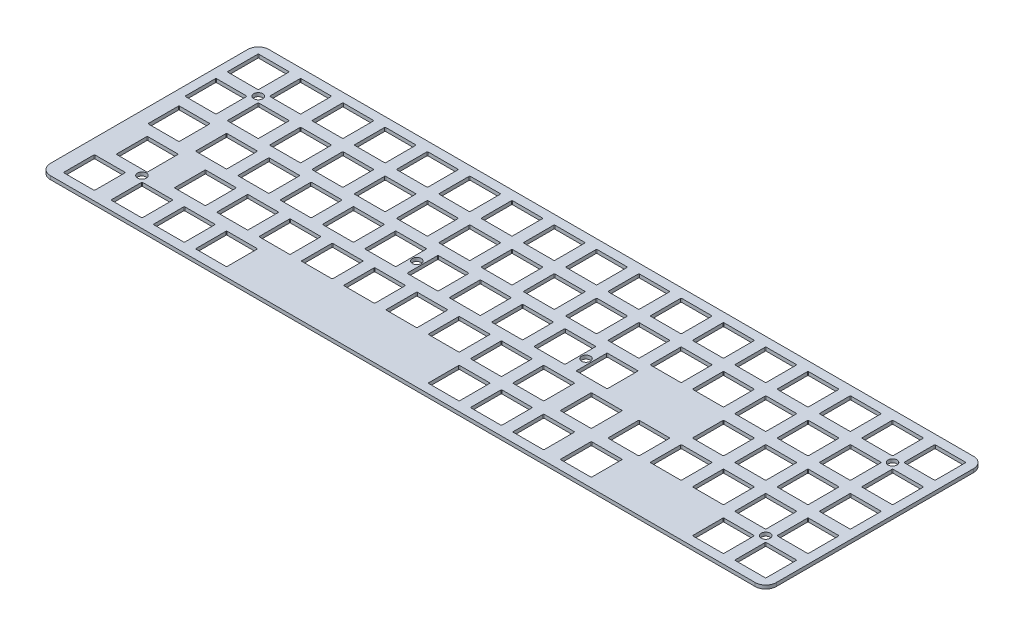
SolidWorks part; units mm, degrees
ref_plane "Front" through (0, 0, 0) normal (0, 0, 1) x (1, 0, 0)
ref_plane "Top" through (0, 0, 0) normal (0, 1, 0) x (1, 0, 0)
ref_plane "Right" through (0, 0, 0) normal (1, 0, 0) x (0, 0, -1)
sketch "Sketch1" plane through (0, 0, 0) normal (0, 1, 0) x (1, 0, 0)
  line L0 (-161.925, 28.575) -> (161.925, 28.575)
  line L1 (161.925, -47.625) -> (-161.925, -47.625)
  line L2 (161.925, -47.625) -> (161.925, 47.625)
  line L3 (161.925, 47.625) -> (-161.925, 47.625)
  line L4 (-161.925, -47.625) -> (-161.925, 47.625)
  line L5 (-123.825, 47.625) -> (-123.825, 28.575)
  line L6 (-104.775, 47.625) -> (-104.775, 28.575)
  line L7 (-142.875, 47.625) -> (-142.875, 28.575)
  line L8 (-85.725, 47.625) -> (-85.725, 28.575)
  line L9 (-66.675, 47.625) -> (-66.675, 28.575)
  line L10 (-47.625, 47.625) -> (-47.625, 28.575)
  line L11 (-28.575, 47.625) -> (-28.575, 28.575)
  line L12 (-9.525, 47.625) -> (-9.525, 28.575)
  line L13 (9.525, 47.625) -> (9.525, 28.575)
  line L14 (28.575, 47.625) -> (28.575, 28.575)
  line L15 (47.625, 47.625) -> (47.625, 28.575)
  line L16 (66.675, 47.625) -> (66.675, 28.575)
  line L17 (85.725, 47.625) -> (85.725, 28.575)
  line L18 (104.775, 47.625) -> (104.775, 28.575)
  line L19 (123.825, 47.625) -> (123.825, 28.575)
  line L20 (142.875, 47.625) -> (142.875, 28.575)
  line L21 (-142.875, 47.625) -> (-123.825, 47.625) construction
  line L22 (-161.925, 9.525) -> (161.925, 9.525)
  line L23 (-142.875, 28.575) -> (-142.875, 9.525)
  line L24 (-123.825, 28.575) -> (-123.825, 9.525)
  line L25 (-104.775, 28.575) -> (-104.775, 9.525)
  line L26 (-85.725, 28.575) -> (-85.725, 9.525)
  line L27 (-66.675, 28.575) -> (-66.675, 9.525)
  line L28 (-47.625, 28.575) -> (-47.625, 9.525)
  line L29 (-28.575, 28.575) -> (-28.575, 9.525)
  line L30 (-9.525, 28.575) -> (-9.525, 9.525)
  line L31 (9.525, 28.575) -> (9.525, 9.525)
  line L32 (28.575, 28.575) -> (28.575, 9.525)
  line L33 (47.625, 28.575) -> (47.625, 9.525)
  line L34 (66.675, 28.575) -> (66.675, 9.525)
  line L35 (85.725, 28.575) -> (85.725, 9.525)
  line L36 (104.775, 28.575) -> (104.775, 9.525)
  line L37 (123.825, 28.575) -> (123.825, 9.525)
  line L38 (142.875, 28.575) -> (142.875, 9.525)
  line L39 (-142.875, 28.575) -> (-123.825, 28.575) construction
  line L40 (-161.925, -9.525) -> (161.925, -9.525)
  line L41 (-161.925, -28.575) -> (161.925, -28.575)
  line L42 (-138.1125, 9.525) -> (-138.1125, -9.525)
  line L43 (-128.5875, -9.525) -> (-128.5875, -28.575)
  line L44 (-138.1125, -28.575) -> (-138.1125, -47.625)
  line L45 (-119.0625, 9.525) -> (-119.0625, -9.525)
  line L46 (-100.0125, 9.525) -> (-100.0125, -9.525)
  line L47 (-80.9625, 9.525) -> (-80.9625, -9.525)
  line L48 (-61.9125, 9.525) -> (-61.9125, -9.525)
  line L49 (-42.8625, 9.525) -> (-42.8625, -9.525)
  line L50 (-23.8125, 9.525) -> (-23.8125, -9.525)
  line L51 (-4.7625, 9.525) -> (-4.7625, -9.525)
  line L52 (14.2875, 9.525) -> (14.2875, -9.525)
  line L53 (33.3375, 9.525) -> (33.3375, -9.525)
  line L54 (-138.1125, 9.525) -> (-119.0625, 9.525) construction
  line L55 (52.3875, 9.525) -> (52.3875, -9.525)
  line L56 (85.725, 9.525) -> (85.725, -9.525)
  line L57 (-109.5375, -9.525) -> (-109.5375, -28.575)
  line L58 (-90.4875, -9.525) -> (-90.4875, -28.575)
  line L59 (-71.4375, -9.525) -> (-71.4375, -28.575)
  line L60 (-52.3875, -9.525) -> (-52.3875, -28.575)
  line L61 (-33.3375, -9.525) -> (-33.3375, -28.575)
  line L62 (-14.2875, -9.525) -> (-14.2875, -28.575)
  line L63 (4.7625, -9.525) -> (4.7625, -28.575)
  line L64 (23.8125, -9.525) -> (23.8125, -28.575)
  line L65 (42.8625, -9.525) -> (42.8625, -28.575)
  line L66 (-128.5875, -9.525) -> (-109.5375, -9.525) construction
  line L67 (66.675, -9.525) -> (66.675, -28.575)
  line L68 (85.725, -9.525) -> (85.725, -28.575)
  line L69 (-119.0625, -28.575) -> (-119.0625, -47.625)
  line L70 (-100.0125, -28.575) -> (-100.0125, -47.625)
  line L71 (-80.9625, -28.575) -> (-80.9625, -47.625)
  line L72 (-138.1125, -28.575) -> (-119.0625, -28.575) construction
  line L73 (-47.625, -28.575) -> (-47.625, -47.625)
  line L74 (4.7625, -28.575) -> (4.7625, -47.625)
  line L75 (23.8125, -28.575) -> (23.8125, -47.625)
  line L76 (42.8625, -28.575) -> (42.8625, -47.625)
  line L77 (61.9125, -28.575) -> (61.9125, -47.625)
  line L78 (85.725, -28.575) -> (85.725, -47.625)
  line L79 (104.775, 9.525) -> (104.775, -9.525)
  line L80 (104.775, -9.525) -> (104.775, -28.575)
  line L81 (123.825, 9.525) -> (123.825, -9.525)
  line L82 (123.825, -9.525) -> (123.825, -28.575)
  line L83 (123.825, -28.575) -> (123.825, -47.625)
  line L84 (142.875, 9.525) -> (142.875, -9.525)
  line L85 (142.875, -9.525) -> (142.875, -28.575)
  line L86 (142.875, -28.575) -> (142.875, -47.625)
  line L87 (-161.925, 47.625) -> (-142.875, 28.575) construction
  line L88 (-142.875, 28.575) -> (-161.925, 9.525) construction
  line L89 (-161.925, 9.525) -> (-138.1125, -9.525) construction
  line L90 (-138.1125, -9.525) -> (-119.0625, 9.525) construction
  line L91 (-119.0625, 9.525) -> (-100.0125, -9.525) construction
  line L92 (-100.0125, -9.525) -> (-80.9625, 9.525) construction
  line L93 (-80.9625, 9.525) -> (-61.9125, -9.525) construction
  line L94 (-61.9125, -9.525) -> (-42.8625, 9.525) construction
  line L95 (-42.8625, 9.525) -> (-23.8125, -9.525) construction
  line L96 (-23.8125, -9.525) -> (-4.7625, 9.525) construction
  line L97 (-4.7625, 9.525) -> (14.2875, -9.525) construction
  line L98 (14.2875, -9.525) -> (33.3375, 9.525) construction
  line L99 (33.3375, 9.525) -> (52.3875, -9.525) construction
  line L100 (52.3875, -9.525) -> (85.725, 9.525) construction
  line L101 (85.725, 9.525) -> (104.775, -9.525) construction
  line L102 (104.775, -9.525) -> (85.725, -28.575) construction
  line L103 (85.725, -47.625) -> (123.825, -28.575) construction
  line L104 (85.725, -28.575) -> (123.825, -47.625) construction
  line L105 (123.825, -28.575) -> (104.775, -9.525) construction
  line L106 (104.775, -9.525) -> (123.825, 9.525) construction
  line L107 (123.825, 9.525) -> (104.775, 28.575) construction
  line L108 (104.775, 28.575) -> (123.825, 47.625) construction
  line L109 (123.825, 47.625) -> (142.875, 28.575) construction
  line L110 (142.875, 28.575) -> (123.825, 9.525) construction
  line L111 (123.825, 9.525) -> (142.875, -9.525) construction
  line L112 (142.875, -9.525) -> (123.825, -28.575) construction
  line L113 (123.825, -28.575) -> (142.875, -47.625) construction
  line L114 (142.875, -47.625) -> (161.925, -28.575) construction
  line L115 (161.925, -28.575) -> (142.875, -9.525) construction
  line L116 (142.875, -9.525) -> (161.925, 9.525) construction
  line L117 (161.925, 9.525) -> (142.875, 28.575) construction
  line L118 (142.875, 28.575) -> (161.925, 47.625) construction
  line L119 (161.925, -47.625) -> (142.875, -28.575) construction
  line L120 (142.875, -28.575) -> (123.825, -47.625) construction
  line L121 (85.725, -47.625) -> (61.9125, -28.575) construction
  line L122 (61.9125, -28.575) -> (42.8625, -47.625) construction
  line L123 (42.8625, -47.625) -> (23.8125, -28.575) construction
  line L124 (23.8125, -28.575) -> (42.8625, -9.525) construction
  line L125 (42.8625, -9.525) -> (66.675, -28.575) construction
  line L126 (66.675, -28.575) -> (85.725, -9.525) construction
  line L127 (85.725, -9.525) -> (104.775, -28.575) construction
  line L128 (104.775, -28.575) -> (123.825, -9.525) construction
  line L129 (123.825, -9.525) -> (142.875, -28.575) construction
  line L130 (142.875, -28.575) -> (161.925, -9.525) construction
  line L131 (161.925, -9.525) -> (142.875, 9.525) construction
  line L132 (142.875, 9.525) -> (123.825, -9.525) construction
  line L133 (123.825, -9.525) -> (104.775, 9.525) construction
  line L134 (104.775, 9.525) -> (85.725, -9.525) construction
  line L135 (85.725, -9.525) -> (52.3875, 9.525) construction
  line L136 (52.3875, 9.525) -> (33.3375, -9.525) construction
  line L137 (33.3375, -9.525) -> (14.2875, 9.525) construction
  line L138 (14.2875, 9.525) -> (-4.7625, -9.525) construction
  line L139 (-4.7625, -9.525) -> (-23.8125, 9.525) construction
  line L140 (-23.8125, 9.525) -> (-42.8625, -9.525) construction
  line L141 (-42.8625, -9.525) -> (-61.9125, 9.525) construction
  line L142 (-61.9125, 9.525) -> (-80.9625, -9.525) construction
  line L143 (-80.9625, -9.525) -> (-100.0125, 9.525) construction
  line L144 (-100.0125, 9.525) -> (-119.0625, -9.525) construction
  line L145 (-119.0625, -9.525) -> (-138.1125, 9.525) construction
  line L146 (-138.1125, 9.525) -> (-161.925, -9.525) construction
  line L147 (-161.925, -9.525) -> (-128.5875, -28.575) construction
  line L148 (-128.5875, -28.575) -> (-109.5375, -9.525) construction
  line L149 (-109.5375, -9.525) -> (-90.4875, -28.575) construction
  line L150 (-90.4875, -28.575) -> (-71.4375, -9.525) construction
  line L151 (-71.4375, -9.525) -> (-52.3875, -28.575) construction
  line L152 (-52.3875, -28.575) -> (-33.3375, -9.525) construction
  line L153 (-33.3375, -9.525) -> (-14.2875, -28.575) construction
  line L154 (-14.2875, -28.575) -> (4.7625, -9.525) construction
  line L155 (4.7625, -9.525) -> (23.8125, -28.575) construction
  line L156 (23.8125, -28.575) -> (4.7625, -47.625) construction
  line L157 (4.7625, -47.625) -> (-47.625, -28.575) construction
  line L158 (-47.625, -28.575) -> (-80.9625, -47.625) construction
  line L159 (-80.9625, -47.625) -> (-100.0125, -28.575) construction
  line L160 (-100.0125, -28.575) -> (-119.0625, -47.625) construction
  line L161 (-119.0625, -47.625) -> (-138.1125, -28.575) construction
  line L162 (-138.1125, -28.575) -> (-161.925, -47.625) construction
  line L163 (-161.925, -28.575) -> (-138.1125, -47.625) construction
  line L164 (-138.1125, -47.625) -> (-119.0625, -28.575) construction
  line L165 (-119.0625, -28.575) -> (-100.0125, -47.625) construction
  line L166 (-100.0125, -47.625) -> (-80.9625, -28.575) construction
  line L167 (-80.9625, -28.575) -> (-47.625, -47.625) construction
  line L168 (-47.625, -47.625) -> (4.7625, -28.575) construction
  line L169 (4.7625, -28.575) -> (23.8125, -47.625) construction
  line L170 (23.8125, -47.625) -> (42.8625, -28.575) construction
  line L171 (42.8625, -28.575) -> (61.9125, -47.625) construction
  line L172 (61.9125, -47.625) -> (85.725, -28.575) construction
  line L173 (85.725, -28.575) -> (66.675, -9.525) construction
  line L174 (66.675, -9.525) -> (42.8625, -28.575) construction
  line L175 (42.8625, -28.575) -> (23.8125, -9.525) construction
  line L176 (23.8125, -9.525) -> (4.7625, -28.575) construction
  line L177 (4.7625, -28.575) -> (-14.2875, -9.525) construction
  line L178 (-14.2875, -9.525) -> (-33.3375, -28.575) construction
  line L179 (-33.3375, -28.575) -> (-52.3875, -9.525) construction
  line L180 (-52.3875, -9.525) -> (-71.4375, -28.575) construction
  line L181 (-71.4375, -28.575) -> (-90.4875, -9.525) construction
  line L182 (-90.4875, -9.525) -> (-109.5375, -28.575) construction
  line L183 (-109.5375, -28.575) -> (-128.5875, -9.525) construction
  line L184 (-128.5875, -9.525) -> (-161.925, -28.575) construction
  line L185 (161.925, 28.575) -> (142.875, 9.525) construction
  line L186 (142.875, 9.525) -> (123.825, 28.575) construction
  line L187 (123.825, 28.575) -> (104.775, 9.525) construction
  line L188 (104.775, 9.525) -> (85.725, 28.575) construction
  line L189 (85.725, 28.575) -> (66.675, 9.525) construction
  line L190 (66.675, 9.525) -> (47.625, 28.575) construction
  line L191 (47.625, 28.575) -> (28.575, 9.525) construction
  line L192 (28.575, 9.525) -> (9.525, 28.575) construction
  line L193 (9.525, 28.575) -> (-9.525, 9.525) construction
  line L194 (-9.525, 9.525) -> (-28.575, 28.575) construction
  line L195 (-28.575, 28.575) -> (-47.625, 9.525) construction
  line L196 (-47.625, 9.525) -> (-66.675, 28.575) construction
  line L197 (-66.675, 28.575) -> (-85.725, 9.525) construction
  line L198 (-85.725, 9.525) -> (-104.775, 28.575) construction
  line L199 (-104.775, 28.575) -> (-123.825, 9.525) construction
  line L200 (-123.825, 9.525) -> (-142.875, 28.575) construction
  line L201 (-161.925, 28.575) -> (-142.875, 9.525) construction
  line L202 (-142.875, 9.525) -> (-123.825, 28.575) construction
  line L203 (-123.825, 28.575) -> (-104.775, 9.525) construction
  line L204 (-104.775, 9.525) -> (-85.725, 28.575) construction
  line L205 (-85.725, 28.575) -> (-66.675, 9.525) construction
  line L206 (-66.675, 9.525) -> (-47.625, 28.575) construction
  line L207 (-47.625, 28.575) -> (-28.575, 9.525) construction
  line L208 (-28.575, 9.525) -> (-9.525, 28.575) construction
  line L209 (-9.525, 28.575) -> (9.525, 9.525) construction
  line L210 (9.525, 9.525) -> (28.575, 28.575) construction
  line L211 (28.575, 28.575) -> (47.625, 9.525) construction
  line L212 (47.625, 9.525) -> (66.675, 28.575) construction
  line L213 (66.675, 28.575) -> (85.725, 9.525) construction
  line L214 (85.725, 9.525) -> (104.775, 28.575) construction
  line L215 (161.925, 28.575) -> (142.875, 47.625) construction
  line L216 (142.875, 47.625) -> (123.825, 28.575) construction
  line L217 (123.825, 28.575) -> (104.775, 47.625) construction
  line L218 (104.775, 47.625) -> (85.725, 28.575) construction
  line L219 (85.725, 28.575) -> (66.675, 47.625) construction
  line L220 (66.675, 47.625) -> (47.625, 28.575) construction
  line L221 (47.625, 28.575) -> (28.575, 47.625) construction
  line L222 (28.575, 47.625) -> (9.525, 28.575) construction
  line L223 (9.525, 28.575) -> (-9.525, 47.625) construction
  line L224 (-9.525, 47.625) -> (-28.575, 28.575) construction
  line L225 (-28.575, 28.575) -> (-47.625, 47.625) construction
  line L226 (-47.625, 47.625) -> (-66.675, 28.575) construction
  line L227 (-66.675, 28.575) -> (-85.725, 47.625) construction
  line L228 (-85.725, 47.625) -> (-104.775, 28.575) construction
  line L229 (-104.775, 28.575) -> (-123.825, 47.625) construction
  line L230 (-123.825, 47.625) -> (-142.875, 28.575) construction
  line L231 (-161.925, 28.575) -> (-142.875, 47.625) construction
  line L232 (-142.875, 47.625) -> (-123.825, 28.575) construction
  line L233 (-123.825, 28.575) -> (-104.775, 47.625) construction
  line L234 (-104.775, 47.625) -> (-85.725, 28.575) construction
  line L235 (-85.725, 28.575) -> (-66.675, 47.625) construction
  line L236 (-66.675, 47.625) -> (-47.625, 28.575) construction
  line L237 (-47.625, 28.575) -> (-28.575, 47.625) construction
  line L238 (-28.575, 47.625) -> (-9.525, 28.575) construction
  line L239 (-9.525, 28.575) -> (9.525, 47.625) construction
  line L240 (9.525, 47.625) -> (28.575, 28.575) construction
  line L241 (28.575, 28.575) -> (47.625, 47.625) construction
  line L242 (47.625, 47.625) -> (66.675, 28.575) construction
  line L243 (66.675, 28.575) -> (85.725, 47.625) construction
  line L244 (85.725, 47.625) -> (104.775, 28.575) construction
  line L245 (160.147, 50.6095) -> (-160.147, 50.6095)
  line L246 (164.9095, 45.847) -> (164.9095, -45.847)
  line L247 (160.147, -50.6095) -> (-160.147, -50.6095)
  line L248 (-164.9095, 45.847) -> (-164.9095, -45.847)
  arc A0 (164.9095, 45.847) -> (160.147, 50.6095) centre (160.147, 45.847) ccw
  arc A1 (160.147, -50.6095) -> (164.9095, -45.847) centre (160.147, -45.847) ccw
  arc A2 (-164.9095, -45.847) -> (-160.147, -50.6095) centre (-160.147, -45.847) ccw
  arc A3 (-160.147, 50.6095) -> (-164.9095, 45.847) centre (-160.147, 45.847) ccw
  point P145 (0, 0)
  point P146 (104.775, -38.1)
  point P147 (-152.4, 38.1)
  point P148 (-152.4, 19.05)
  point P149 (-150.0188, 0)
  point P150 (-145.2562, -19.05)
  point P151 (-150.0188, -38.1)
  point P152 (-128.5875, -38.1)
  point P153 (-119.0625, -19.05)
  point P154 (-128.5875, 0)
  point P155 (-133.35, 19.05)
  point P156 (-133.35, 38.1)
  point P157 (-114.3, 38.1)
  point P158 (-114.3, 19.05)
  point P159 (-109.5375, 0)
  point P160 (-100.0125, -19.05)
  point P161 (-90.4875, -38.1)
  point P162 (-109.5375, -38.1)
  point P163 (-64.2938, -38.1)
  point P164 (-21.4312, -38.1)
  point P165 (14.2875, -38.1)
  point P166 (33.3375, -38.1)
  point P167 (52.3875, -38.1)
  point P168 (73.8188, -38.1)
  point P169 (133.35, -38.1)
  point P170 (152.4, -38.1)
  point P171 (152.4, -19.05)
  point P172 (133.35, -19.05)
  point P173 (114.3, -19.05)
  point P174 (95.25, -19.05)
  point P175 (76.2, -19.05)
  point P176 (54.7687, -19.05)
  point P177 (33.3375, -19.05)
  point P178 (14.2875, -19.05)
  point P179 (-4.7625, -19.05)
  point P180 (-23.8125, -19.05)
  point P181 (-42.8625, -19.05)
  point P182 (-61.9125, -19.05)
  point P183 (-80.9625, -19.05)
  point P184 (-90.4875, 0)
  point P185 (-71.4375, 0)
  point P186 (-52.3875, 0)
  point P187 (-33.3375, 0)
  point P188 (-14.2875, 0)
  point P189 (4.7625, 0)
  point P190 (23.8125, 0)
  point P191 (42.8625, 0)
  point P192 (69.0563, 0)
  point P193 (95.25, 0)
  point P194 (114.3, 0)
  point P195 (133.35, 0)
  point P196 (152.4, 0)
  point P197 (152.4, 19.05)
  point P198 (133.35, 19.05)
  point P199 (114.3, 19.05)
  point P200 (95.25, 19.05)
  point P201 (76.2, 19.05)
  point P202 (57.15, 19.05)
  point P203 (38.1, 19.05)
  point P204 (19.05, 19.05)
  point P205 (0, 19.05)
  point P206 (-19.05, 19.05)
  point P207 (-38.1, 19.05)
  point P208 (-57.15, 19.05)
  point P209 (-76.2, 19.05)
  point P210 (-95.25, 19.05)
  point P211 (-95.25, 38.1)
  point P212 (-76.2, 38.1)
  point P213 (-57.15, 38.1)
  point P214 (-38.1, 38.1)
  point P215 (-19.05, 38.1)
  point P216 (0, 38.1)
  point P217 (19.05, 38.1)
  point P218 (38.1, 38.1)
  point P219 (57.15, 38.1)
  point P220 (76.2, 38.1)
  point P221 (95.25, 38.1)
  point P222 (114.3, 38.1)
  point P223 (133.35, 38.1)
  point P224 (152.4, 38.1)
  point P225 (-152.4, 38.1)
  point P226 (0, 0)
sketch "Sketch2" plane through (0, 0, 0) normal (0, 1, 0) x (1, 0, 0)
  line L0 (-161.925, 28.575) -> (-142.875, 47.625) construction
  line L1 (-145.7071, 45.0977) -> (-159.0929, 45.0977)
  line L2 (-145.4023, 44.7929) -> (-145.4023, 31.4071)
  line L3 (-145.7071, 31.1023) -> (-159.0929, 31.1023)
  line L4 (-159.3977, 44.7929) -> (-159.3977, 31.4071)
  line L5 (-152.4, 31.1023) -> (-152.4, 45.0977) construction
  line L6 (-145.4023, 38.1) -> (-159.3977, 38.1) construction
  line L7 (-126.3523, 38.1) -> (-140.3477, 38.1) construction
  line L8 (-133.35, 31.1023) -> (-133.35, 45.0977) construction
  line L9 (-126.6571, 45.0977) -> (-140.0429, 45.0977)
  line L10 (-126.3523, 44.7929) -> (-126.3523, 31.4071)
  line L11 (-140.3477, 44.7929) -> (-140.3477, 31.4071)
  line L12 (-126.6571, 31.1023) -> (-140.0429, 31.1023)
  line L13 (-107.3023, 38.1) -> (-121.2977, 38.1) construction
  line L14 (-114.3, 31.1023) -> (-114.3, 45.0977) construction
  line L15 (-107.6071, 45.0977) -> (-120.9929, 45.0977)
  line L16 (-107.3023, 44.7929) -> (-107.3023, 31.4071)
  line L17 (-121.2977, 44.7929) -> (-121.2977, 31.4071)
  line L18 (-107.6071, 31.1023) -> (-120.9929, 31.1023)
  line L19 (-88.2523, 38.1) -> (-102.2477, 38.1) construction
  line L20 (-95.25, 31.1023) -> (-95.25, 45.0977) construction
  line L21 (-88.5571, 45.0977) -> (-101.9429, 45.0977)
  line L22 (-88.2523, 44.7929) -> (-88.2523, 31.4071)
  line L23 (-102.2477, 44.7929) -> (-102.2477, 31.4071)
  line L24 (-88.5571, 31.1023) -> (-101.9429, 31.1023)
  line L25 (-69.2023, 38.1) -> (-83.1977, 38.1) construction
  line L26 (-76.2, 31.1023) -> (-76.2, 45.0977) construction
  line L27 (-69.5071, 45.0977) -> (-82.8929, 45.0977)
  line L28 (-69.2023, 44.7929) -> (-69.2023, 31.4071)
  line L29 (-83.1977, 44.7929) -> (-83.1977, 31.4071)
  line L30 (-69.5071, 31.1023) -> (-82.8929, 31.1023)
  line L31 (-50.1523, 38.1) -> (-64.1477, 38.1) construction
  line L32 (-57.15, 31.1023) -> (-57.15, 45.0977) construction
  line L33 (-50.4571, 45.0977) -> (-63.8429, 45.0977)
  line L34 (-50.1523, 44.7929) -> (-50.1523, 31.4071)
  line L35 (-64.1477, 44.7929) -> (-64.1477, 31.4071)
  line L36 (-50.4571, 31.1023) -> (-63.8429, 31.1023)
  line L37 (-31.1023, 38.1) -> (-45.0977, 38.1) construction
  line L38 (-38.1, 31.1023) -> (-38.1, 45.0977) construction
  line L39 (-31.4071, 45.0977) -> (-44.7929, 45.0977)
  line L40 (-31.1023, 44.7929) -> (-31.1023, 31.4071)
  line L41 (-45.0977, 44.7929) -> (-45.0977, 31.4071)
  line L42 (-31.4071, 31.1023) -> (-44.7929, 31.1023)
  line L43 (-12.0523, 38.1) -> (-26.0477, 38.1) construction
  line L44 (-19.05, 31.1023) -> (-19.05, 45.0977) construction
  line L45 (-12.3571, 45.0977) -> (-25.7429, 45.0977)
  line L46 (-12.0523, 44.7929) -> (-12.0523, 31.4071)
  line L47 (-26.0477, 44.7929) -> (-26.0477, 31.4071)
  line L48 (-12.3571, 31.1023) -> (-25.7429, 31.1023)
  line L49 (6.9977, 38.1) -> (-6.9977, 38.1) construction
  line L50 (0, 31.1023) -> (0, 45.0977) construction
  line L51 (6.6929, 45.0977) -> (-6.6929, 45.0977)
  line L52 (6.9977, 44.7929) -> (6.9977, 31.4071)
  line L53 (-6.9977, 44.7929) -> (-6.9977, 31.4071)
  line L54 (6.6929, 31.1023) -> (-6.6929, 31.1023)
  line L55 (26.0477, 38.1) -> (12.0523, 38.1) construction
  line L56 (19.05, 31.1023) -> (19.05, 45.0977) construction
  line L57 (25.7429, 45.0977) -> (12.3571, 45.0977)
  line L58 (26.0477, 44.7929) -> (26.0477, 31.4071)
  line L59 (12.0523, 44.7929) -> (12.0523, 31.4071)
  line L60 (25.7429, 31.1023) -> (12.3571, 31.1023)
  line L61 (45.0977, 38.1) -> (31.1023, 38.1) construction
  line L62 (38.1, 31.1023) -> (38.1, 45.0977) construction
  line L63 (44.7929, 45.0977) -> (31.4071, 45.0977)
  line L64 (45.0977, 44.7929) -> (45.0977, 31.4071)
  line L65 (31.1023, 44.7929) -> (31.1023, 31.4071)
  line L66 (44.7929, 31.1023) -> (31.4071, 31.1023)
  line L67 (64.1477, 38.1) -> (50.1523, 38.1) construction
  line L68 (57.15, 31.1023) -> (57.15, 45.0977) construction
  line L69 (63.8429, 45.0977) -> (50.4571, 45.0977)
  line L70 (64.1477, 44.7929) -> (64.1477, 31.4071)
  line L71 (50.1523, 44.7929) -> (50.1523, 31.4071)
  line L72 (63.8429, 31.1023) -> (50.4571, 31.1023)
  line L73 (83.1977, 38.1) -> (69.2023, 38.1) construction
  line L74 (76.2, 31.1023) -> (76.2, 45.0977) construction
  line L75 (82.8929, 45.0977) -> (69.5071, 45.0977)
  line L76 (83.1977, 44.7929) -> (83.1977, 31.4071)
  line L77 (69.2023, 44.7929) -> (69.2023, 31.4071)
  line L78 (82.8929, 31.1023) -> (69.5071, 31.1023)
  line L79 (102.2477, 38.1) -> (88.2523, 38.1) construction
  line L80 (95.25, 31.1023) -> (95.25, 45.0977) construction
  line L81 (101.9429, 45.0977) -> (88.5571, 45.0977)
  line L82 (102.2477, 44.7929) -> (102.2477, 31.4071)
  line L83 (88.2523, 44.7929) -> (88.2523, 31.4071)
  line L84 (101.9429, 31.1023) -> (88.5571, 31.1023)
  line L85 (121.2977, 38.1) -> (107.3023, 38.1) construction
  line L86 (114.3, 31.1023) -> (114.3, 45.0977) construction
  line L87 (120.9929, 45.0977) -> (107.6071, 45.0977)
  line L88 (121.2977, 44.7929) -> (121.2977, 31.4071)
  line L89 (107.3023, 44.7929) -> (107.3023, 31.4071)
  line L90 (120.9929, 31.1023) -> (107.6071, 31.1023)
  line L91 (140.3477, 38.1) -> (126.3523, 38.1) construction
  line L92 (133.35, 31.1023) -> (133.35, 45.0977) construction
  line L93 (140.0429, 45.0977) -> (126.6571, 45.0977)
  line L94 (140.3477, 44.7929) -> (140.3477, 31.4071)
  line L95 (126.3523, 44.7929) -> (126.3523, 31.4071)
  line L96 (140.0429, 31.1023) -> (126.6571, 31.1023)
  line L97 (159.3977, 38.1) -> (145.4023, 38.1) construction
  line L98 (152.4, 31.1023) -> (152.4, 45.0977) construction
  line L99 (159.0929, 45.0977) -> (145.7071, 45.0977)
  line L100 (159.3977, 44.7929) -> (159.3977, 31.4071)
  line L101 (145.4023, 44.7929) -> (145.4023, 31.4071)
  line L102 (159.0929, 31.1023) -> (145.7071, 31.1023)
  line L103 (-126.3523, 19.05) -> (-140.3477, 19.05) construction
  line L104 (-133.35, 12.0523) -> (-133.35, 26.0477) construction
  line L105 (-126.6571, 26.0477) -> (-140.0429, 26.0477)
  line L106 (-126.3523, 25.7429) -> (-126.3523, 12.3571)
  line L107 (-140.3477, 25.7429) -> (-140.3477, 12.3571)
  line L108 (-126.6571, 12.0523) -> (-140.0429, 12.0523)
  line L109 (-107.3023, 19.05) -> (-121.2977, 19.05) construction
  line L110 (-114.3, 12.0523) -> (-114.3, 26.0477) construction
  line L111 (-107.6071, 26.0477) -> (-120.9929, 26.0477)
  line L112 (-107.3023, 25.7429) -> (-107.3023, 12.3571)
  line L113 (-121.2977, 25.7429) -> (-121.2977, 12.3571)
  line L114 (-107.6071, 12.0523) -> (-120.9929, 12.0523)
  line L115 (-88.2523, 19.05) -> (-102.2477, 19.05) construction
  line L116 (-95.25, 12.0523) -> (-95.25, 26.0477) construction
  line L117 (-88.5571, 26.0477) -> (-101.9429, 26.0477)
  line L118 (-88.2523, 25.7429) -> (-88.2523, 12.3571)
  line L119 (-102.2477, 25.7429) -> (-102.2477, 12.3571)
  line L120 (-88.5571, 12.0523) -> (-101.9429, 12.0523)
  line L121 (-69.2023, 19.05) -> (-83.1977, 19.05) construction
  line L122 (-76.2, 12.0523) -> (-76.2, 26.0477) construction
  line L123 (-69.5071, 26.0477) -> (-82.8929, 26.0477)
  line L124 (-69.2023, 25.7429) -> (-69.2023, 12.3571)
  line L125 (-83.1977, 25.7429) -> (-83.1977, 12.3571)
  line L126 (-69.5071, 12.0523) -> (-82.8929, 12.0523)
  line L127 (-50.1523, 19.05) -> (-64.1477, 19.05) construction
  line L128 (-57.15, 12.0523) -> (-57.15, 26.0477) construction
  line L129 (-50.4571, 26.0477) -> (-63.8429, 26.0477)
  line L130 (-50.1523, 25.7429) -> (-50.1523, 12.3571)
  line L131 (-64.1477, 25.7429) -> (-64.1477, 12.3571)
  line L132 (-50.4571, 12.0523) -> (-63.8429, 12.0523)
  line L133 (-31.1023, 19.05) -> (-45.0977, 19.05) construction
  line L134 (-38.1, 12.0523) -> (-38.1, 26.0477) construction
  line L135 (-31.4071, 26.0477) -> (-44.7929, 26.0477)
  line L136 (-31.1023, 25.7429) -> (-31.1023, 12.3571)
  line L137 (-45.0977, 25.7429) -> (-45.0977, 12.3571)
  line L138 (-31.4071, 12.0523) -> (-44.7929, 12.0523)
  line L139 (-12.0523, 19.05) -> (-26.0477, 19.05) construction
  line L140 (-19.05, 12.0523) -> (-19.05, 26.0477) construction
  line L141 (-12.3571, 26.0477) -> (-25.7429, 26.0477)
  line L142 (-12.0523, 25.7429) -> (-12.0523, 12.3571)
  line L143 (-26.0477, 25.7429) -> (-26.0477, 12.3571)
  line L144 (-12.3571, 12.0523) -> (-25.7429, 12.0523)
  line L145 (6.9977, 19.05) -> (-6.9977, 19.05) construction
  line L146 (0, 12.0523) -> (0, 26.0477) construction
  line L147 (6.6929, 26.0477) -> (-6.6929, 26.0477)
  line L148 (6.9977, 25.7429) -> (6.9977, 12.3571)
  line L149 (-6.9977, 25.7429) -> (-6.9977, 12.3571)
  line L150 (6.6929, 12.0523) -> (-6.6929, 12.0523)
  line L151 (26.0477, 19.05) -> (12.0523, 19.05) construction
  line L152 (19.05, 12.0523) -> (19.05, 26.0477) construction
  line L153 (25.7429, 26.0477) -> (12.3571, 26.0477)
  line L154 (26.0477, 25.7429) -> (26.0477, 12.3571)
  line L155 (12.0523, 25.7429) -> (12.0523, 12.3571)
  line L156 (25.7429, 12.0523) -> (12.3571, 12.0523)
  line L157 (45.0977, 19.05) -> (31.1023, 19.05) construction
  line L158 (38.1, 12.0523) -> (38.1, 26.0477) construction
  line L159 (44.7929, 26.0477) -> (31.4071, 26.0477)
  line L160 (45.0977, 25.7429) -> (45.0977, 12.3571)
  line L161 (31.1023, 25.7429) -> (31.1023, 12.3571)
  line L162 (44.7929, 12.0523) -> (31.4071, 12.0523)
  line L163 (64.1477, 19.05) -> (50.1523, 19.05) construction
  line L164 (57.15, 12.0523) -> (57.15, 26.0477) construction
  line L165 (63.8429, 26.0477) -> (50.4571, 26.0477)
  line L166 (64.1477, 25.7429) -> (64.1477, 12.3571)
  line L167 (50.1523, 25.7429) -> (50.1523, 12.3571)
  line L168 (63.8429, 12.0523) -> (50.4571, 12.0523)
  line L169 (83.1977, 19.05) -> (69.2023, 19.05) construction
  line L170 (76.2, 12.0523) -> (76.2, 26.0477) construction
  line L171 (82.8929, 26.0477) -> (69.5071, 26.0477)
  line L172 (83.1977, 25.7429) -> (83.1977, 12.3571)
  line L173 (69.2023, 25.7429) -> (69.2023, 12.3571)
  line L174 (82.8929, 12.0523) -> (69.5071, 12.0523)
  line L175 (102.2477, 19.05) -> (88.2523, 19.05) construction
  line L176 (95.25, 12.0523) -> (95.25, 26.0477) construction
  line L177 (101.9429, 26.0477) -> (88.5571, 26.0477)
  line L178 (102.2477, 25.7429) -> (102.2477, 12.3571)
  line L179 (88.2523, 25.7429) -> (88.2523, 12.3571)
  line L180 (101.9429, 12.0523) -> (88.5571, 12.0523)
  line L181 (121.2977, 19.05) -> (107.3023, 19.05) construction
  line L182 (114.3, 12.0523) -> (114.3, 26.0477) construction
  line L183 (120.9929, 26.0477) -> (107.6071, 26.0477)
  line L184 (121.2977, 25.7429) -> (121.2977, 12.3571)
  line L185 (107.3023, 25.7429) -> (107.3023, 12.3571)
  line L186 (120.9929, 12.0523) -> (107.6071, 12.0523)
  line L187 (140.3477, 19.05) -> (126.3523, 19.05) construction
  line L188 (133.35, 12.0523) -> (133.35, 26.0477) construction
  line L189 (140.0429, 26.0477) -> (126.6571, 26.0477)
  line L190 (140.3477, 25.7429) -> (140.3477, 12.3571)
  line L191 (126.3523, 25.7429) -> (126.3523, 12.3571)
  line L192 (140.0429, 12.0523) -> (126.6571, 12.0523)
  line L193 (159.3977, 19.05) -> (145.4023, 19.05) construction
  line L194 (152.4, 12.0523) -> (152.4, 26.0477) construction
  line L195 (159.0929, 26.0477) -> (145.7071, 26.0477)
  line L196 (159.3977, 25.7429) -> (159.3977, 12.3571)
  line L197 (145.4023, 25.7429) -> (145.4023, 12.3571)
  line L198 (159.0929, 12.0523) -> (145.7071, 12.0523)
  line L199 (-145.4023, 19.05) -> (-159.3977, 19.05) construction
  line L200 (-152.4, 12.0523) -> (-152.4, 26.0477) construction
  line L201 (-145.7071, 26.0477) -> (-159.0929, 26.0477)
  line L202 (-145.4023, 25.7429) -> (-145.4023, 12.3571)
  line L203 (-159.3977, 25.7429) -> (-159.3977, 12.3571)
  line L204 (-145.7071, 12.0523) -> (-159.0929, 12.0523)
  line L205 (-100.0125, -26.0477) -> (-100.0125, -12.0523) construction
  line L210 (-138.1125, 9.525) -> (-161.925, -9.525) construction
  line L211 (-157.0164, -6.9977) -> (-143.021, -6.9977)
  line L212 (-157.0164, -6.9977) -> (-157.0164, 6.9977)
  line L213 (-138.2585, -12.0523) -> (-152.254, -12.0523)
  line L214 (-138.2585, -12.0523) -> (-138.2585, -26.0477)
  line L215 (-138.2585, -26.0477) -> (-152.254, -26.0477)
  line L216 (-152.254, -12.0523) -> (-152.254, -26.0477)
  line L217 (-145.2562, -26.0477) -> (-145.2562, -12.0523) construction
  line L218 (-138.2586, -19.05) -> (-152.254, -19.05) construction
  line L219 (-157.0164, 6.9977) -> (-143.021, 6.9977)
  line L220 (-143.021, -6.9977) -> (-143.021, 6.9977)
  line L221 (-150.0187, 6.9977) -> (-150.0187, -6.9977) construction
  line L222 (-157.0164, 0) -> (-143.021, 0) construction
  line L223 (-138.1125, -28.575) -> (-161.925, -47.625) construction
  line L224 (-143.021, -31.1023) -> (-157.0164, -31.1023)
  line L225 (-143.021, -31.1023) -> (-143.021, -45.0977)
  line L226 (-143.021, -45.0977) -> (-157.0164, -45.0977)
  line L227 (-157.0164, -31.1023) -> (-157.0164, -45.0977)
  line L228 (-150.0187, -45.0977) -> (-150.0187, -31.1023) construction
  line L229 (-143.021, -38.1) -> (-157.0164, -38.1) construction
  line L230 (-128.5875, -28.575) -> (-109.5375, -9.525) construction
  line L231 (-121.5898, 6.9977) -> (-135.5852, 6.9977)
  line L232 (-121.5898, 6.9977) -> (-121.5898, -6.9977)
  line L233 (-121.5898, -6.9977) -> (-135.5852, -6.9977)
  line L234 (-135.5852, 6.9977) -> (-135.5852, -6.9977)
  line L235 (-128.5875, -6.9977) -> (-128.5875, 6.9977) construction
  line L236 (-121.5898, 0) -> (-135.5852, 0) construction
  line L237 (-112.0648, -12.0523) -> (-126.0602, -12.0523)
  line L238 (-112.0648, -12.0523) -> (-112.0648, -26.0477)
  line L239 (-112.0648, -26.0477) -> (-126.0602, -26.0477)
  line L240 (-126.0602, -12.0523) -> (-126.0602, -26.0477)
  line L241 (-119.0625, -26.0477) -> (-119.0625, -12.0523) construction
  line L242 (-112.0648, -19.05) -> (-126.0602, -19.05) construction
  line L243 (-138.1125, -47.625) -> (-119.0625, -28.575) construction
  line L244 (-135.5852, -45.0977) -> (-121.5898, -45.0977)
  line L245 (-135.5852, -45.0977) -> (-135.5852, -31.1023)
  line L246 (-135.5852, -31.1023) -> (-121.5898, -31.1023)
  line L247 (-121.5898, -45.0977) -> (-121.5898, -31.1023)
  line L248 (-128.5875, -31.1023) -> (-128.5875, -45.0977) construction
  line L249 (-135.5852, -38.1) -> (-121.5898, -38.1) construction
  line L250 (-102.5398, -6.9977) -> (-116.5352, -6.9977)
  line L251 (-102.5398, 6.9977) -> (-102.5398, -6.9977)
  line L252 (-102.5398, 6.9977) -> (-116.5352, 6.9977)
  line L253 (-116.5352, 6.9977) -> (-116.5352, -6.9977)
  line L254 (-102.5398, 0) -> (-116.5352, 0) construction
  line L255 (-109.5375, -6.9977) -> (-109.5375, 6.9977) construction
  line L256 (-83.4898, -6.9977) -> (-97.4852, -6.9977)
  line L257 (-83.4898, 6.9977) -> (-83.4898, -6.9977)
  line L258 (-83.4898, 6.9977) -> (-97.4852, 6.9977)
  line L259 (-97.4852, 6.9977) -> (-97.4852, -6.9977)
  line L260 (-83.4898, 0) -> (-97.4852, 0) construction
  line L261 (-90.4875, -6.9977) -> (-90.4875, 6.9977) construction
  line L262 (-64.4398, -6.9977) -> (-78.4352, -6.9977)
  line L263 (-64.4398, 6.9977) -> (-64.4398, -6.9977)
  line L264 (-64.4398, 6.9977) -> (-78.4352, 6.9977)
  line L265 (-78.4352, 6.9977) -> (-78.4352, -6.9977)
  line L266 (-64.4398, 0) -> (-78.4352, 0) construction
  line L267 (-71.4375, -6.9977) -> (-71.4375, 6.9977) construction
  line L268 (-45.3898, -6.9977) -> (-59.3852, -6.9977)
  line L269 (-45.3898, 6.9977) -> (-45.3898, -6.9977)
  line L270 (-45.3898, 6.9977) -> (-59.3852, 6.9977)
  line L271 (-59.3852, 6.9977) -> (-59.3852, -6.9977)
  line L272 (-45.3898, 0) -> (-59.3852, 0) construction
  line L273 (-52.3875, -6.9977) -> (-52.3875, 6.9977) construction
  line L274 (-26.3398, -6.9977) -> (-40.3352, -6.9977)
  line L275 (-26.3398, 6.9977) -> (-26.3398, -6.9977)
  line L276 (-26.3398, 6.9977) -> (-40.3352, 6.9977)
  line L277 (-40.3352, 6.9977) -> (-40.3352, -6.9977)
  line L278 (-26.3398, 0) -> (-40.3352, 0) construction
  line L279 (-33.3375, -6.9977) -> (-33.3375, 6.9977) construction
  line L280 (-7.2898, -6.9977) -> (-21.2852, -6.9977)
  line L281 (-7.2898, 6.9977) -> (-7.2898, -6.9977)
  line L282 (-7.2898, 6.9977) -> (-21.2852, 6.9977)
  line L283 (-21.2852, 6.9977) -> (-21.2852, -6.9977)
  line L284 (-7.2898, 0) -> (-21.2852, 0) construction
  line L285 (-14.2875, -6.9977) -> (-14.2875, 6.9977) construction
  line L286 (11.7602, -6.9977) -> (-2.2352, -6.9977)
  line L287 (11.7602, 6.9977) -> (11.7602, -6.9977)
  line L288 (11.7602, 6.9977) -> (-2.2352, 6.9977)
  line L289 (-2.2352, 6.9977) -> (-2.2352, -6.9977)
  line L290 (11.7602, 0) -> (-2.2352, 0) construction
  line L291 (4.7625, -6.9977) -> (4.7625, 6.9977) construction
  line L292 (30.8102, -6.9977) -> (16.8148, -6.9977)
  line L293 (30.8102, 6.9977) -> (30.8102, -6.9977)
  line L294 (30.8102, 6.9977) -> (16.8148, 6.9977)
  line L295 (16.8148, 6.9977) -> (16.8148, -6.9977)
  line L296 (30.8102, 0) -> (16.8148, 0) construction
  line L297 (23.8125, -6.9977) -> (23.8125, 6.9977) construction
  line L298 (49.8602, -6.9977) -> (35.8648, -6.9977)
  line L299 (49.8602, 6.9977) -> (49.8602, -6.9977)
  line L300 (49.8602, 6.9977) -> (35.8648, 6.9977)
  line L301 (35.8648, 6.9977) -> (35.8648, -6.9977)
  line L302 (49.8602, 0) -> (35.8648, 0) construction
  line L303 (42.8625, -6.9977) -> (42.8625, 6.9977) construction
  line L304 (-93.0148, -19.05) -> (-107.0102, -19.05) construction
  line L305 (-93.0148, -12.0523) -> (-107.0102, -12.0523)
  line L306 (-93.0148, -12.0523) -> (-93.0148, -26.0477)
  line L307 (-93.0148, -26.0477) -> (-107.0102, -26.0477)
  line L308 (-107.0102, -12.0523) -> (-107.0102, -26.0477)
  line L309 (-80.9625, -26.0477) -> (-80.9625, -12.0523) construction
  line L310 (-73.9648, -19.05) -> (-87.9602, -19.05) construction
  line L311 (-73.9648, -12.0523) -> (-87.9602, -12.0523)
  line L312 (-73.9648, -12.0523) -> (-73.9648, -26.0477)
  line L313 (-73.9648, -26.0477) -> (-87.9602, -26.0477)
  line L314 (-87.9602, -12.0523) -> (-87.9602, -26.0477)
  line L315 (-61.9125, -26.0477) -> (-61.9125, -12.0523) construction
  line L316 (-54.9148, -19.05) -> (-68.9102, -19.05) construction
  line L317 (-54.9148, -12.0523) -> (-68.9102, -12.0523)
  line L318 (-54.9148, -12.0523) -> (-54.9148, -26.0477)
  line L319 (-54.9148, -26.0477) -> (-68.9102, -26.0477)
  line L320 (-68.9102, -12.0523) -> (-68.9102, -26.0477)
  line L321 (-42.8625, -26.0477) -> (-42.8625, -12.0523) construction
  line L322 (-35.8648, -19.05) -> (-49.8602, -19.05) construction
  line L323 (-35.8648, -12.0523) -> (-49.8602, -12.0523)
  line L324 (-35.8648, -12.0523) -> (-35.8648, -26.0477)
  line L325 (-35.8648, -26.0477) -> (-49.8602, -26.0477)
  line L326 (-49.8602, -12.0523) -> (-49.8602, -26.0477)
  line L327 (-23.8125, -26.0477) -> (-23.8125, -12.0523) construction
  line L328 (-16.8148, -19.05) -> (-30.8102, -19.05) construction
  line L329 (-16.8148, -12.0523) -> (-30.8102, -12.0523)
  line L330 (-16.8148, -12.0523) -> (-16.8148, -26.0477)
  line L331 (-16.8148, -26.0477) -> (-30.8102, -26.0477)
  line L332 (-30.8102, -12.0523) -> (-30.8102, -26.0477)
  line L333 (-4.7625, -26.0477) -> (-4.7625, -12.0523) construction
  line L334 (2.2352, -19.05) -> (-11.7602, -19.05) construction
  line L335 (2.2352, -12.0523) -> (-11.7602, -12.0523)
  line L336 (2.2352, -12.0523) -> (2.2352, -26.0477)
  line L337 (2.2352, -26.0477) -> (-11.7602, -26.0477)
  line L338 (-11.7602, -12.0523) -> (-11.7602, -26.0477)
  line L339 (14.2875, -26.0477) -> (14.2875, -12.0523) construction
  line L340 (21.2852, -19.05) -> (7.2898, -19.05) construction
  line L341 (21.2852, -12.0523) -> (7.2898, -12.0523)
  line L342 (21.2852, -12.0523) -> (21.2852, -26.0477)
  line L343 (21.2852, -26.0477) -> (7.2898, -26.0477)
  line L344 (7.2898, -12.0523) -> (7.2898, -26.0477)
  line L345 (33.3375, -26.0477) -> (33.3375, -12.0523) construction
  line L346 (40.3352, -19.05) -> (26.3398, -19.05) construction
  line L347 (40.3352, -12.0523) -> (26.3398, -12.0523)
  line L348 (40.3352, -12.0523) -> (40.3352, -26.0477)
  line L349 (40.3352, -26.0477) -> (26.3398, -26.0477)
  line L350 (26.3398, -12.0523) -> (26.3398, -26.0477)
  line L353 (-100.0125, -28.575) -> (-119.0625, -47.625) construction
  line L354 (-116.5352, -45.0977) -> (-102.5398, -45.0977)
  line L358 (-116.5352, -45.0977) -> (-116.5352, -31.1023)
  line L359 (-116.5352, -31.1023) -> (-102.5398, -31.1023)
  line L362 (-102.5398, -45.0977) -> (-102.5398, -31.1023)
  line L364 (-109.5375, -31.1023) -> (-109.5375, -45.0977) construction
  line L371 (-116.5352, -38.1) -> (-102.5398, -38.1) construction
  line L373 (-100.0125, -47.625) -> (-80.9625, -28.575) construction
  line L376 (-97.4852, -45.0977) -> (-83.4898, -45.0977)
  line L378 (-97.4852, -45.0977) -> (-97.4852, -31.1023)
  line L381 (101.9429, -6.9977) -> (88.5571, -6.9977)
  line L382 (-97.4852, -31.1023) -> (-83.4898, -31.1023)
  line L383 (-83.4898, -45.0977) -> (-83.4898, -31.1023)
  line L384 (-90.4875, -31.1023) -> (-90.4875, -45.0977) construction
  line L385 (-97.4852, -38.1) -> (-83.4898, -38.1) construction
  line L386 (23.8125, -47.625) -> (42.8625, -28.575) construction
  line L387 (7.2898, -45.0977) -> (21.2852, -45.0977)
  line L388 (7.2898, -45.0977) -> (7.2898, -31.1023)
  line L389 (7.2898, -31.1023) -> (21.2852, -31.1023)
  line L390 (21.2852, -45.0977) -> (21.2852, -31.1023)
  line L391 (14.2875, -31.1023) -> (14.2875, -45.0977) construction
  line L392 (7.2898, -38.1) -> (21.2852, -38.1) construction
  line L393 (26.3398, -45.0977) -> (40.3352, -45.0977)
  line L394 (26.3398, -45.0977) -> (26.3398, -31.1023)
  line L395 (26.3398, -31.1023) -> (40.3352, -31.1023)
  line L396 (40.3352, -45.0977) -> (40.3352, -31.1023)
  line L397 (33.3375, -31.1023) -> (33.3375, -45.0977) construction
  line L398 (26.3398, -38.1) -> (40.3352, -38.1) construction
  line L399 (61.9125, -28.575) -> (42.8625, -47.625) construction
  line L400 (45.3898, -45.0977) -> (59.3852, -45.0977)
  line L401 (45.3898, -45.0977) -> (45.3898, -31.1023)
  line L402 (45.3898, -31.1023) -> (59.3852, -31.1023)
  line L403 (59.3852, -45.0977) -> (59.3852, -31.1023)
  line L404 (52.3875, -31.1023) -> (52.3875, -45.0977) construction
  line L405 (45.3898, -38.1) -> (59.3852, -38.1) construction
  line L406 (102.2477, 6.6929) -> (102.2477, -6.6929)
  line L407 (66.821, -45.0977) -> (80.8165, -45.0977)
  line L408 (66.821, -45.0977) -> (66.821, -31.1023)
  line L409 (66.821, -31.1023) -> (80.8165, -31.1023)
  line L410 (80.8165, -45.0977) -> (80.8165, -31.1023)
  line L411 (73.8188, -31.1023) -> (73.8188, -45.0977) construction
  line L412 (66.821, -38.1) -> (80.8165, -38.1) construction
  line L413 (101.9429, 6.9977) -> (88.5571, 6.9977)
  line L414 (88.2523, 6.6929) -> (88.2523, -6.6929)
  line L415 (95.25, -6.9977) -> (95.25, 6.9977) construction
  line L416 (102.2477, 0) -> (88.2523, 0) construction
  line L417 (120.9929, -6.9977) -> (107.6071, -6.9977)
  line L418 (114.3, -6.9977) -> (114.3, 6.9977) construction
  line L419 (121.2977, 0) -> (107.3023, 0) construction
  line L420 (120.9929, 6.9977) -> (107.6071, 6.9977)
  line L421 (107.3023, 6.6929) -> (107.3023, -6.6929)
  line L422 (121.2977, 6.6929) -> (121.2977, -6.6929)
  line L423 (140.0429, 6.9977) -> (126.6571, 6.9977)
  line L424 (126.3523, 6.6929) -> (126.3523, -6.6929)
  line L425 (133.35, -6.9977) -> (133.35, 6.9977) construction
  line L426 (140.3477, 0) -> (126.3523, 0) construction
  line L427 (140.3477, 6.6929) -> (140.3477, -6.6929)
  line L428 (140.0429, -6.9977) -> (126.6571, -6.9977)
  line L429 (159.3977, 6.6929) -> (159.3977, -6.6929)
  line L430 (159.0929, -6.9977) -> (145.7071, -6.9977)
  line L431 (152.4, -6.9977) -> (152.4, 6.9977) construction
  line L432 (145.4023, 6.6929) -> (145.4023, -6.6929)
  line L433 (159.3977, 0) -> (145.4023, 0) construction
  line L434 (159.0929, 6.9977) -> (145.7071, 6.9977)
  line L435 (101.9429, -26.0477) -> (88.5571, -26.0477)
  line L436 (102.2477, -12.3571) -> (102.2477, -25.7429)
  line L437 (101.9429, -12.0523) -> (88.5571, -12.0523)
  line L438 (88.2523, -12.3571) -> (88.2523, -25.7429)
  line L439 (95.25, -26.0477) -> (95.25, -12.0523) construction
  line L440 (102.2477, -19.05) -> (88.2523, -19.05) construction
  line L441 (120.9929, -26.0477) -> (107.6071, -26.0477)
  line L442 (114.3, -26.0477) -> (114.3, -12.0523) construction
  line L443 (121.2977, -19.05) -> (107.3023, -19.05) construction
  line L444 (120.9929, -12.0523) -> (107.6071, -12.0523)
  line L445 (107.3023, -12.3571) -> (107.3023, -25.7429)
  line L446 (121.2977, -12.3571) -> (121.2977, -25.7429)
  line L447 (140.0429, -12.0523) -> (126.6571, -12.0523)
  line L448 (126.3523, -12.3571) -> (126.3523, -25.7429)
  line L449 (133.35, -26.0477) -> (133.35, -12.0523) construction
  line L450 (140.3477, -19.05) -> (126.3523, -19.05) construction
  line L451 (140.3477, -12.3571) -> (140.3477, -25.7429)
  line L452 (140.0429, -26.0477) -> (126.6571, -26.0477)
  line L453 (159.3977, -12.3571) -> (159.3977, -25.7429)
  line L454 (159.0929, -26.0477) -> (145.7071, -26.0477)
  line L455 (152.4, -26.0477) -> (152.4, -12.0523) construction
  line L456 (145.4023, -12.3571) -> (145.4023, -25.7429)
  line L457 (159.3977, -19.05) -> (145.4023, -19.05) construction
  line L458 (159.0929, -12.0523) -> (145.7071, -12.0523)
  line L459 (85.725, -28.575) -> (66.675, -9.525) construction
  line L460 (145.4023, -45.0977) -> (159.3977, -45.0977)
  line L461 (145.4023, -45.0977) -> (145.4023, -31.1023)
  line L462 (145.4023, -31.1023) -> (159.3977, -31.1023)
  line L463 (159.3977, -45.0977) -> (159.3977, -31.1023)
  line L464 (152.4, -31.1023) -> (152.4, -45.0977) construction
  line L465 (145.4023, -38.1) -> (159.3977, -38.1) construction
  line L466 (126.3523, -45.0977) -> (140.3477, -45.0977)
  line L467 (126.3523, -45.0977) -> (126.3523, -31.1023)
  line L468 (126.3523, -31.1023) -> (140.3477, -31.1023)
  line L469 (140.3477, -45.0977) -> (140.3477, -31.1023)
  line L470 (133.35, -31.1023) -> (133.35, -45.0977) construction
  line L471 (126.3523, -38.1) -> (140.3477, -38.1) construction
  line L472 (69.2023, -26.0477) -> (83.1977, -26.0477)
  line L473 (69.2023, -26.0477) -> (69.2023, -12.0523)
  line L474 (69.2023, -12.0523) -> (83.1977, -12.0523)
  line L475 (83.1977, -26.0477) -> (83.1977, -12.0523)
  line L476 (76.2, -12.0523) -> (76.2, -26.0477) construction
  line L477 (69.2023, -19.05) -> (83.1977, -19.05) construction
  line L478 (-145.7071, 31.4071) -> (-140.0429, 25.7429) construction
  line L479 (47.771, -26.0477) -> (61.7665, -26.0477)
  line L480 (47.771, -26.0477) -> (47.771, -12.0523)
  line L481 (47.771, -12.0523) -> (61.7665, -12.0523)
  line L482 (61.7665, -26.0477) -> (61.7665, -12.0523)
  line L483 (54.7687, -12.0523) -> (54.7687, -26.0477) construction
  line L484 (47.771, -19.05) -> (61.7665, -19.05) construction
  line L489 (-140.0429, 31.4071) -> (-145.7071, 25.7429) construction
  line L490 (158.75, -49.2125) -> (-158.75, -49.2125)
  line L491 (140.0429, 31.4071) -> (145.7071, 25.7429) construction
  line L496 (163.5125, -44.45) -> (163.5125, 44.45)
  line L497 (158.75, 49.2125) -> (-158.75, 49.2125)
  line L498 (145.7071, 31.4071) -> (140.0429, 25.7429) construction
  line L503 (-163.5125, -44.45) -> (-163.5125, 44.45)
  line L504 (0, 49.2125) -> (0, -49.2125) construction
  line L505 (-45.3898, 6.9977) -> (-40.3352, 6.9977) construction
  line L510 (163.5125, 0) -> (-163.5125, 0) construction
  line L511 (-42.8625, 6.9977) -> (-42.8625, 0) construction
  line L512 (30.8102, 6.9977) -> (35.8648, 6.9977) construction
  line L513 (33.3375, 6.9977) -> (33.3375, 0) construction
  arc A0 (-145.4023, 31.4071) -> (-145.7071, 31.1023) centre (-145.7071, 31.4071) cw
  arc A1 (-145.7071, 45.0977) -> (-145.4023, 44.7929) centre (-145.7071, 44.7929) cw
  arc A2 (-159.0929, 45.0977) -> (-159.3977, 44.7929) centre (-159.0929, 44.7929) ccw
  arc A3 (-159.0929, 31.1023) -> (-159.3977, 31.4071) centre (-159.0929, 31.4071) cw
  arc A4 (-126.6571, 45.0977) -> (-126.3523, 44.7929) centre (-126.6571, 44.7929) cw
  arc A5 (-140.0429, 45.0977) -> (-140.3477, 44.7929) centre (-140.0429, 44.7929) ccw
  arc A6 (-140.0429, 31.1023) -> (-140.3477, 31.4071) centre (-140.0429, 31.4071) cw
  arc A7 (-126.3523, 31.4071) -> (-126.6571, 31.1023) centre (-126.6571, 31.4071) cw
  arc A8 (-107.6071, 45.0977) -> (-107.3023, 44.7929) centre (-107.6071, 44.7929) cw
  arc A9 (-120.9929, 45.0977) -> (-121.2977, 44.7929) centre (-120.9929, 44.7929) ccw
  arc A10 (-120.9929, 31.1023) -> (-121.2977, 31.4071) centre (-120.9929, 31.4071) cw
  arc A11 (-107.3023, 31.4071) -> (-107.6071, 31.1023) centre (-107.6071, 31.4071) cw
  arc A12 (-88.5571, 45.0977) -> (-88.2523, 44.7929) centre (-88.5571, 44.7929) cw
  arc A13 (-101.9429, 45.0977) -> (-102.2477, 44.7929) centre (-101.9429, 44.7929) ccw
  arc A14 (-101.9429, 31.1023) -> (-102.2477, 31.4071) centre (-101.9429, 31.4071) cw
  arc A15 (-88.2523, 31.4071) -> (-88.5571, 31.1023) centre (-88.5571, 31.4071) cw
  arc A16 (-69.5071, 45.0977) -> (-69.2023, 44.7929) centre (-69.5071, 44.7929) cw
  arc A17 (-82.8929, 45.0977) -> (-83.1977, 44.7929) centre (-82.8929, 44.7929) ccw
  arc A18 (-82.8929, 31.1023) -> (-83.1977, 31.4071) centre (-82.8929, 31.4071) cw
  arc A19 (-69.2023, 31.4071) -> (-69.5071, 31.1023) centre (-69.5071, 31.4071) cw
  arc A20 (-50.4571, 45.0977) -> (-50.1523, 44.7929) centre (-50.4571, 44.7929) cw
  arc A21 (-63.8429, 45.0977) -> (-64.1477, 44.7929) centre (-63.8429, 44.7929) ccw
  arc A22 (-63.8429, 31.1023) -> (-64.1477, 31.4071) centre (-63.8429, 31.4071) cw
  arc A23 (-50.1523, 31.4071) -> (-50.4571, 31.1023) centre (-50.4571, 31.4071) cw
  arc A24 (-31.4071, 45.0977) -> (-31.1023, 44.7929) centre (-31.4071, 44.7929) cw
  arc A25 (-44.7929, 45.0977) -> (-45.0977, 44.7929) centre (-44.7929, 44.7929) ccw
  arc A26 (-44.7929, 31.1023) -> (-45.0977, 31.4071) centre (-44.7929, 31.4071) cw
  arc A27 (-31.1023, 31.4071) -> (-31.4071, 31.1023) centre (-31.4071, 31.4071) cw
  arc A28 (-12.3571, 45.0977) -> (-12.0523, 44.7929) centre (-12.3571, 44.7929) cw
  arc A29 (-25.7429, 45.0977) -> (-26.0477, 44.7929) centre (-25.7429, 44.7929) ccw
  arc A30 (-25.7429, 31.1023) -> (-26.0477, 31.4071) centre (-25.7429, 31.4071) cw
  arc A31 (-12.0523, 31.4071) -> (-12.3571, 31.1023) centre (-12.3571, 31.4071) cw
  arc A32 (6.6929, 45.0977) -> (6.9977, 44.7929) centre (6.6929, 44.7929) cw
  arc A33 (-6.6929, 45.0977) -> (-6.9977, 44.7929) centre (-6.6929, 44.7929) ccw
  arc A34 (-6.6929, 31.1023) -> (-6.9977, 31.4071) centre (-6.6929, 31.4071) cw
  arc A35 (6.9977, 31.4071) -> (6.6929, 31.1023) centre (6.6929, 31.4071) cw
  arc A36 (25.7429, 45.0977) -> (26.0477, 44.7929) centre (25.7429, 44.7929) cw
  arc A37 (12.3571, 45.0977) -> (12.0523, 44.7929) centre (12.3571, 44.7929) ccw
  arc A38 (12.3571, 31.1023) -> (12.0523, 31.4071) centre (12.3571, 31.4071) cw
  arc A39 (26.0477, 31.4071) -> (25.7429, 31.1023) centre (25.7429, 31.4071) cw
  arc A40 (44.7929, 45.0977) -> (45.0977, 44.7929) centre (44.7929, 44.7929) cw
  arc A41 (31.4071, 45.0977) -> (31.1023, 44.7929) centre (31.4071, 44.7929) ccw
  arc A42 (31.4071, 31.1023) -> (31.1023, 31.4071) centre (31.4071, 31.4071) cw
  arc A43 (45.0977, 31.4071) -> (44.7929, 31.1023) centre (44.7929, 31.4071) cw
  arc A44 (63.8429, 45.0977) -> (64.1477, 44.7929) centre (63.8429, 44.7929) cw
  arc A45 (50.4571, 45.0977) -> (50.1523, 44.7929) centre (50.4571, 44.7929) ccw
  arc A46 (50.4571, 31.1023) -> (50.1523, 31.4071) centre (50.4571, 31.4071) cw
  arc A47 (64.1477, 31.4071) -> (63.8429, 31.1023) centre (63.8429, 31.4071) cw
  arc A48 (82.8929, 45.0977) -> (83.1977, 44.7929) centre (82.8929, 44.7929) cw
  arc A49 (69.5071, 45.0977) -> (69.2023, 44.7929) centre (69.5071, 44.7929) ccw
  arc A50 (69.5071, 31.1023) -> (69.2023, 31.4071) centre (69.5071, 31.4071) cw
  arc A51 (83.1977, 31.4071) -> (82.8929, 31.1023) centre (82.8929, 31.4071) cw
  arc A52 (101.9429, 45.0977) -> (102.2477, 44.7929) centre (101.9429, 44.7929) cw
  arc A53 (88.5571, 45.0977) -> (88.2523, 44.7929) centre (88.5571, 44.7929) ccw
  arc A54 (88.5571, 31.1023) -> (88.2523, 31.4071) centre (88.5571, 31.4071) cw
  arc A55 (102.2477, 31.4071) -> (101.9429, 31.1023) centre (101.9429, 31.4071) cw
  arc A56 (120.9929, 45.0977) -> (121.2977, 44.7929) centre (120.9929, 44.7929) cw
  arc A57 (107.6071, 45.0977) -> (107.3023, 44.7929) centre (107.6071, 44.7929) ccw
  arc A58 (107.6071, 31.1023) -> (107.3023, 31.4071) centre (107.6071, 31.4071) cw
  arc A59 (121.2977, 31.4071) -> (120.9929, 31.1023) centre (120.9929, 31.4071) cw
  arc A60 (140.0429, 45.0977) -> (140.3477, 44.7929) centre (140.0429, 44.7929) cw
  arc A61 (126.6571, 45.0977) -> (126.3523, 44.7929) centre (126.6571, 44.7929) ccw
  arc A62 (126.6571, 31.1023) -> (126.3523, 31.4071) centre (126.6571, 31.4071) cw
  arc A63 (140.3477, 31.4071) -> (140.0429, 31.1023) centre (140.0429, 31.4071) cw
  arc A64 (159.0929, 45.0977) -> (159.3977, 44.7929) centre (159.0929, 44.7929) cw
  arc A65 (145.7071, 45.0977) -> (145.4023, 44.7929) centre (145.7071, 44.7929) ccw
  arc A66 (145.7071, 31.1023) -> (145.4023, 31.4071) centre (145.7071, 31.4071) cw
  arc A67 (159.3977, 31.4071) -> (159.0929, 31.1023) centre (159.0929, 31.4071) cw
  arc A68 (-126.6571, 26.0477) -> (-126.3523, 25.7429) centre (-126.6571, 25.7429) cw
  arc A69 (-140.0429, 26.0477) -> (-140.3477, 25.7429) centre (-140.0429, 25.7429) ccw
  arc A70 (-140.0429, 12.0523) -> (-140.3477, 12.3571) centre (-140.0429, 12.3571) cw
  arc A71 (-126.3523, 12.3571) -> (-126.6571, 12.0523) centre (-126.6571, 12.3571) cw
  arc A72 (-107.6071, 26.0477) -> (-107.3023, 25.7429) centre (-107.6071, 25.7429) cw
  arc A73 (-120.9929, 26.0477) -> (-121.2977, 25.7429) centre (-120.9929, 25.7429) ccw
  arc A74 (-120.9929, 12.0523) -> (-121.2977, 12.3571) centre (-120.9929, 12.3571) cw
  arc A75 (-107.3023, 12.3571) -> (-107.6071, 12.0523) centre (-107.6071, 12.3571) cw
  arc A76 (-88.5571, 26.0477) -> (-88.2523, 25.7429) centre (-88.5571, 25.7429) cw
  arc A77 (-101.9429, 26.0477) -> (-102.2477, 25.7429) centre (-101.9429, 25.7429) ccw
  arc A78 (-101.9429, 12.0523) -> (-102.2477, 12.3571) centre (-101.9429, 12.3571) cw
  arc A79 (-88.2523, 12.3571) -> (-88.5571, 12.0523) centre (-88.5571, 12.3571) cw
  arc A80 (-69.5071, 26.0477) -> (-69.2023, 25.7429) centre (-69.5071, 25.7429) cw
  arc A81 (-82.8929, 26.0477) -> (-83.1977, 25.7429) centre (-82.8929, 25.7429) ccw
  arc A82 (-82.8929, 12.0523) -> (-83.1977, 12.3571) centre (-82.8929, 12.3571) cw
  arc A83 (-69.2023, 12.3571) -> (-69.5071, 12.0523) centre (-69.5071, 12.3571) cw
  arc A84 (-50.4571, 26.0477) -> (-50.1523, 25.7429) centre (-50.4571, 25.7429) cw
  arc A85 (-63.8429, 26.0477) -> (-64.1477, 25.7429) centre (-63.8429, 25.7429) ccw
  arc A86 (-63.8429, 12.0523) -> (-64.1477, 12.3571) centre (-63.8429, 12.3571) cw
  arc A87 (-50.1523, 12.3571) -> (-50.4571, 12.0523) centre (-50.4571, 12.3571) cw
  arc A88 (-31.4071, 26.0477) -> (-31.1023, 25.7429) centre (-31.4071, 25.7429) cw
  arc A89 (-44.7929, 26.0477) -> (-45.0977, 25.7429) centre (-44.7929, 25.7429) ccw
  arc A90 (-44.7929, 12.0523) -> (-45.0977, 12.3571) centre (-44.7929, 12.3571) cw
  arc A91 (-31.1023, 12.3571) -> (-31.4071, 12.0523) centre (-31.4071, 12.3571) cw
  arc A92 (-12.3571, 26.0477) -> (-12.0523, 25.7429) centre (-12.3571, 25.7429) cw
  arc A93 (-25.7429, 26.0477) -> (-26.0477, 25.7429) centre (-25.7429, 25.7429) ccw
  arc A94 (-25.7429, 12.0523) -> (-26.0477, 12.3571) centre (-25.7429, 12.3571) cw
  arc A95 (-12.0523, 12.3571) -> (-12.3571, 12.0523) centre (-12.3571, 12.3571) cw
  arc A96 (6.6929, 26.0477) -> (6.9977, 25.7429) centre (6.6929, 25.7429) cw
  arc A97 (-6.6929, 26.0477) -> (-6.9977, 25.7429) centre (-6.6929, 25.7429) ccw
  arc A98 (-6.6929, 12.0523) -> (-6.9977, 12.3571) centre (-6.6929, 12.3571) cw
  arc A99 (6.9977, 12.3571) -> (6.6929, 12.0523) centre (6.6929, 12.3571) cw
  arc A100 (25.7429, 26.0477) -> (26.0477, 25.7429) centre (25.7429, 25.7429) cw
  arc A101 (12.3571, 26.0477) -> (12.0523, 25.7429) centre (12.3571, 25.7429) ccw
  arc A102 (12.3571, 12.0523) -> (12.0523, 12.3571) centre (12.3571, 12.3571) cw
  arc A103 (26.0477, 12.3571) -> (25.7429, 12.0523) centre (25.7429, 12.3571) cw
  arc A104 (44.7929, 26.0477) -> (45.0977, 25.7429) centre (44.7929, 25.7429) cw
  arc A105 (31.4071, 26.0477) -> (31.1023, 25.7429) centre (31.4071, 25.7429) ccw
  arc A106 (31.4071, 12.0523) -> (31.1023, 12.3571) centre (31.4071, 12.3571) cw
  arc A107 (45.0977, 12.3571) -> (44.7929, 12.0523) centre (44.7929, 12.3571) cw
  arc A108 (63.8429, 26.0477) -> (64.1477, 25.7429) centre (63.8429, 25.7429) cw
  arc A109 (50.4571, 26.0477) -> (50.1523, 25.7429) centre (50.4571, 25.7429) ccw
  arc A110 (50.4571, 12.0523) -> (50.1523, 12.3571) centre (50.4571, 12.3571) cw
  arc A111 (64.1477, 12.3571) -> (63.8429, 12.0523) centre (63.8429, 12.3571) cw
  arc A112 (82.8929, 26.0477) -> (83.1977, 25.7429) centre (82.8929, 25.7429) cw
  arc A113 (69.5071, 26.0477) -> (69.2023, 25.7429) centre (69.5071, 25.7429) ccw
  arc A114 (69.5071, 12.0523) -> (69.2023, 12.3571) centre (69.5071, 12.3571) cw
  arc A115 (83.1977, 12.3571) -> (82.8929, 12.0523) centre (82.8929, 12.3571) cw
  arc A116 (101.9429, 26.0477) -> (102.2477, 25.7429) centre (101.9429, 25.7429) cw
  arc A117 (88.5571, 26.0477) -> (88.2523, 25.7429) centre (88.5571, 25.7429) ccw
  arc A118 (88.5571, 12.0523) -> (88.2523, 12.3571) centre (88.5571, 12.3571) cw
  arc A119 (102.2477, 12.3571) -> (101.9429, 12.0523) centre (101.9429, 12.3571) cw
  arc A120 (120.9929, 26.0477) -> (121.2977, 25.7429) centre (120.9929, 25.7429) cw
  arc A121 (107.6071, 26.0477) -> (107.3023, 25.7429) centre (107.6071, 25.7429) ccw
  arc A122 (107.6071, 12.0523) -> (107.3023, 12.3571) centre (107.6071, 12.3571) cw
  arc A123 (121.2977, 12.3571) -> (120.9929, 12.0523) centre (120.9929, 12.3571) cw
  arc A124 (140.0429, 26.0477) -> (140.3477, 25.7429) centre (140.0429, 25.7429) cw
  arc A125 (126.6571, 26.0477) -> (126.3523, 25.7429) centre (126.6571, 25.7429) ccw
  arc A126 (126.6571, 12.0523) -> (126.3523, 12.3571) centre (126.6571, 12.3571) cw
  arc A127 (140.3477, 12.3571) -> (140.0429, 12.0523) centre (140.0429, 12.3571) cw
  arc A128 (159.0929, 26.0477) -> (159.3977, 25.7429) centre (159.0929, 25.7429) cw
  arc A129 (145.7071, 26.0477) -> (145.4023, 25.7429) centre (145.7071, 25.7429) ccw
  arc A130 (145.7071, 12.0523) -> (145.4023, 12.3571) centre (145.7071, 12.3571) cw
  arc A131 (159.3977, 12.3571) -> (159.0929, 12.0523) centre (159.0929, 12.3571) cw
  arc A132 (-145.7071, 26.0477) -> (-145.4023, 25.7429) centre (-145.7071, 25.7429) cw
  arc A133 (-159.0929, 26.0477) -> (-159.3977, 25.7429) centre (-159.0929, 25.7429) ccw
  arc A134 (-159.0929, 12.0523) -> (-159.3977, 12.3571) centre (-159.0929, 12.3571) cw
  arc A135 (-145.4023, 12.3571) -> (-145.7071, 12.0523) centre (-145.7071, 12.3571) cw
  arc A136 (101.9429, 6.9977) -> (102.2477, 6.6929) centre (101.9429, 6.6929) cw
  arc A137 (107.6071, 6.9977) -> (107.3023, 6.6929) centre (107.6071, 6.6929) ccw
  arc A138 (107.6071, -6.9977) -> (107.3023, -6.6929) centre (107.6071, -6.6929) cw
  arc A139 (102.2477, -6.6929) -> (101.9429, -6.9977) centre (101.9429, -6.6929) cw
  arc A140 (88.5571, -6.9977) -> (88.2523, -6.6929) centre (88.5571, -6.6929) cw
  arc A141 (88.5571, 6.9977) -> (88.2523, 6.6929) centre (88.5571, 6.6929) ccw
  arc A142 (121.2977, -6.6929) -> (120.9929, -6.9977) centre (120.9929, -6.6929) cw
  arc A143 (120.9929, 6.9977) -> (121.2977, 6.6929) centre (120.9929, 6.6929) cw
  arc A144 (126.6571, 6.9977) -> (126.3523, 6.6929) centre (126.6571, 6.6929) ccw
  arc A145 (140.0429, 6.9977) -> (140.3477, 6.6929) centre (140.0429, 6.6929) cw
  arc A146 (140.3477, -6.6929) -> (140.0429, -6.9977) centre (140.0429, -6.6929) cw
  arc A147 (126.6571, -6.9977) -> (126.3523, -6.6929) centre (126.6571, -6.6929) cw
  arc A148 (159.3977, -6.6929) -> (159.0929, -6.9977) centre (159.0929, -6.6929) cw
  arc A149 (145.7071, -6.9977) -> (145.4023, -6.6929) centre (145.7071, -6.6929) cw
  arc A150 (159.0929, 6.9977) -> (159.3977, 6.6929) centre (159.0929, 6.6929) cw
  arc A151 (145.7071, 6.9977) -> (145.4023, 6.6929) centre (145.7071, 6.6929) ccw
  arc A152 (101.9429, -12.0523) -> (102.2477, -12.3571) centre (101.9429, -12.3571) cw
  arc A153 (107.6071, -12.0523) -> (107.3023, -12.3571) centre (107.6071, -12.3571) ccw
  arc A154 (107.6071, -26.0477) -> (107.3023, -25.7429) centre (107.6071, -25.7429) cw
  arc A155 (102.2477, -25.7429) -> (101.9429, -26.0477) centre (101.9429, -25.7429) cw
  arc A156 (88.5571, -26.0477) -> (88.2523, -25.7429) centre (88.5571, -25.7429) cw
  arc A157 (88.5571, -12.0523) -> (88.2523, -12.3571) centre (88.5571, -12.3571) ccw
  arc A158 (121.2977, -25.7429) -> (120.9929, -26.0477) centre (120.9929, -25.7429) cw
  arc A159 (120.9929, -12.0523) -> (121.2977, -12.3571) centre (120.9929, -12.3571) cw
  arc A160 (126.6571, -12.0523) -> (126.3523, -12.3571) centre (126.6571, -12.3571) ccw
  arc A161 (140.0429, -12.0523) -> (140.3477, -12.3571) centre (140.0429, -12.3571) cw
  arc A162 (140.3477, -25.7429) -> (140.0429, -26.0477) centre (140.0429, -25.7429) cw
  arc A163 (126.6571, -26.0477) -> (126.3523, -25.7429) centre (126.6571, -25.7429) cw
  arc A164 (159.3977, -25.7429) -> (159.0929, -26.0477) centre (159.0929, -25.7429) cw
  arc A165 (145.7071, -26.0477) -> (145.4023, -25.7429) centre (145.7071, -25.7429) cw
  arc A166 (159.0929, -12.0523) -> (159.3977, -12.3571) centre (159.0929, -12.3571) cw
  arc A167 (145.7071, -12.0523) -> (145.4023, -12.3571) centre (145.7071, -12.3571) ccw
  arc A168 (163.5125, 44.45) -> (158.75, 49.2125) centre (158.75, 44.45) ccw
  arc A169 (158.75, -49.2125) -> (163.5125, -44.45) centre (158.75, -44.45) ccw
  arc A170 (-158.75, -49.2125) -> (-163.5125, -44.45) centre (-158.75, -44.45) cw
  arc A171 (-158.75, 49.2125) -> (-163.5125, 44.45) centre (-158.75, 44.45) ccw
  circle A172 centre (-142.875, 28.575) radius 2
  circle A173 centre (-138.1125, -28.575) radius 2
  circle A174 centre (142.875, 28.575) radius 2
  circle A175 centre (142.875, -28.575) radius 2
  circle A176 centre (-42.8625, 0) radius 2
  circle A177 centre (33.3375, 0) radius 2
  point P0 (-152.4, 38.1)
  point P15 (-159.3977, 31.1023)
  point P16 (-150.0187, 0)
  point P552 (-109.5375, -38.1)
  point P558 (-145.2562, -19.05)
  point P562 (-150.0187, -38.1)
  point P568 (-128.5875, 0)
  point P572 (-119.0625, -19.05)
  point P578 (-128.5875, -38.1)
  point P759 (-90.4875, -38.1)
  point P765 (14.2875, -38.1)
  point P769 (33.3375, -38.1)
  point P775 (52.3875, -38.1)
  point P781 (73.8188, -38.1)
  point P786 (152.4, -38.1)
  point P950 (133.35, -38.1)
  point P954 (76.2, -19.05)
  point P960 (54.7687, -19.05)
  point P964 (0, 0)
  point P970 (163.5125, 49.2125)
  point P978 (-163.5125, 49.2125)
  point P981 (-142.875, 28.575)
  point P986 (142.875, 28.575)
  dimension "D1" = 0.3048
  dimension "D10" = 4.7625
  dimension "D11" = 4
  dimension "D13" = 4.7625
  dimension "D2" = 13.9954
  dimension "D8" = 327.025
  dimension "D9" = 98.425
  dimension "D12" = 57.15
  dimension "D3" = 17
  dimension "D4" = 2
  dimension "D5" = 10
  dimension "D6" = 9
  dimension "D7" = 3
extrude "Boss-Extrude1" add sketch "Sketch2" along normal mid plane 1.5875
fillet "Fillet1" radius 0.3048 132 edges at (47.771, 0, 12.0523) (47.771, 0, 26.0477) (61.7665, 0, 26.0477) (61.7665, 0, 12.0523) (69.2023, 0, 12.0523) (69.2023, 0, 26.0477) (83.1977, 0, 26.0477) (83.1977, 0, 12.0523) (126.3523, 0, 31.1023) (126.3523, 0, 45.0977) (140.3477, 0, 45.0977) (140.3477, 0, 31.1023) (145.4023, 0, 31.1023) (145.4023, 0, 45.0977) (159.3977, 0, 45.0977) (159.3977, 0, 31.1023) (66.821, 0, 31.1023) (66.821, 0, 45.0977) (80.8165, 0, 45.0977) (80.8165, 0, 31.1023) (45.3898, 0, 31.1023) (45.3898, 0, 45.0977) (59.3852, 0, 45.0977) (59.3852, 0, 31.1023) (26.3398, 0, 31.1023) (26.3398, 0, 45.0977) (40.3352, 0, 45.0977) (40.3352, 0, 31.1023) (7.2898, 0, 31.1023) (7.2898, 0, 45.0977) (21.2852, 0, 45.0977) (21.2852, 0, 31.1023) (-97.4852, 0, 31.1023) (-97.4852, 0, 45.0977) (-83.4898, 0, 45.0977) (-83.4898, 0, 31.1023) (40.3352, 0, 26.0477) (40.3352, 0, 12.0523) (26.3398, 0, 12.0523) (26.3398, 0, 26.0477) (21.2852, 0, 26.0477) (21.2852, 0, 12.0523) (7.2898, 0, 12.0523) (7.2898, 0, 26.0477) (2.2352, 0, 26.0477) (2.2352, 0, 12.0523) (-11.7602, 0, 12.0523) (-11.7602, 0, 26.0477) (-16.8148, 0, 26.0477) (-16.8148, 0, 12.0523) (-30.8102, 0, 12.0523) (-30.8102, 0, 26.0477) (-35.8648, 0, 26.0477) (-35.8648, 0, 12.0523) (-49.8602, 0, 12.0523) (-49.8602, 0, 26.0477) (-54.9148, 0, 26.0477) (-54.9148, 0, 12.0523) (-68.9102, 0, 12.0523) (-68.9102, 0, 26.0477) (-73.9648, 0, 26.0477) (-73.9648, 0, 12.0523) (-87.9602, 0, 12.0523) (-87.9602, 0, 26.0477) (49.8602, 0, 6.9977) (49.8602, 0, -6.9977) (35.8648, 0, -6.9977) (35.8648, 0, 6.9977) (30.8102, 0, 6.9977) (30.8102, 0, -6.9977) (16.8148, 0, -6.9977) (16.8148, 0, 6.9977) (11.7602, 0, 6.9977) (11.7602, 0, -6.9977) (-2.2352, 0, -6.9977) (-2.2352, 0, 6.9977) (-7.2898, 0, 6.9977) (-7.2898, 0, -6.9977) (-21.2852, 0, -6.9977) (-21.2852, 0, 6.9977) (-26.3398, 0, 6.9977) (-26.3398, 0, -6.9977) (-40.3352, 0, -6.9977) (-40.3352, 0, 6.9977) (-45.3898, 0, 6.9977) (-45.3898, 0, -6.9977) (-59.3852, 0, -6.9977) (-59.3852, 0, 6.9977) (-64.4398, 0, 6.9977) (-64.4398, 0, -6.9977) (-78.4352, 0, -6.9977) (-78.4352, 0, 6.9977) (-83.4898, 0, 6.9977) (-83.4898, 0, -6.9977) (-97.4852, 0, -6.9977) (-97.4852, 0, 6.9977) (-102.5398, 0, 6.9977) (-102.5398, 0, -6.9977) (-116.5352, 0, -6.9977) (-116.5352, 0, 6.9977) (-93.0148, 0, 26.0477) (-93.0148, 0, 12.0523) (-107.0102, 0, 12.0523) (-107.0102, 0, 26.0477) (-116.5352, 0, 31.1023) (-116.5352, 0, 45.0977) (-102.5398, 0, 45.0977) (-102.5398, 0, 31.1023) (-135.5852, 0, 31.1023) (-135.5852, 0, 45.0977) (-121.5898, 0, 45.0977) (-121.5898, 0, 31.1023) (-112.0648, 0, 26.0477) (-112.0648, 0, 12.0523) (-126.0602, 0, 12.0523) (-126.0602, 0, 26.0477) (-121.5898, 0, 6.9977) (-135.5852, 0, -6.9977) (-135.5852, 0, 6.9977) (-143.021, 0, 45.0977) (-143.021, 0, 31.1023) (-157.0164, 0, 31.1023) (-157.0164, 0, 45.0977) (-138.2585, 0, 26.0477) (-138.2585, 0, 12.0523) (-152.254, 0, 12.0523) (-152.254, 0, 26.0477) (-157.0164, 0, -6.9977) (-157.0164, 0, 6.9977) (-143.021, 0, 6.9977) (-121.5898, 0, -6.9977) (-143.021, 0, -6.9977)
